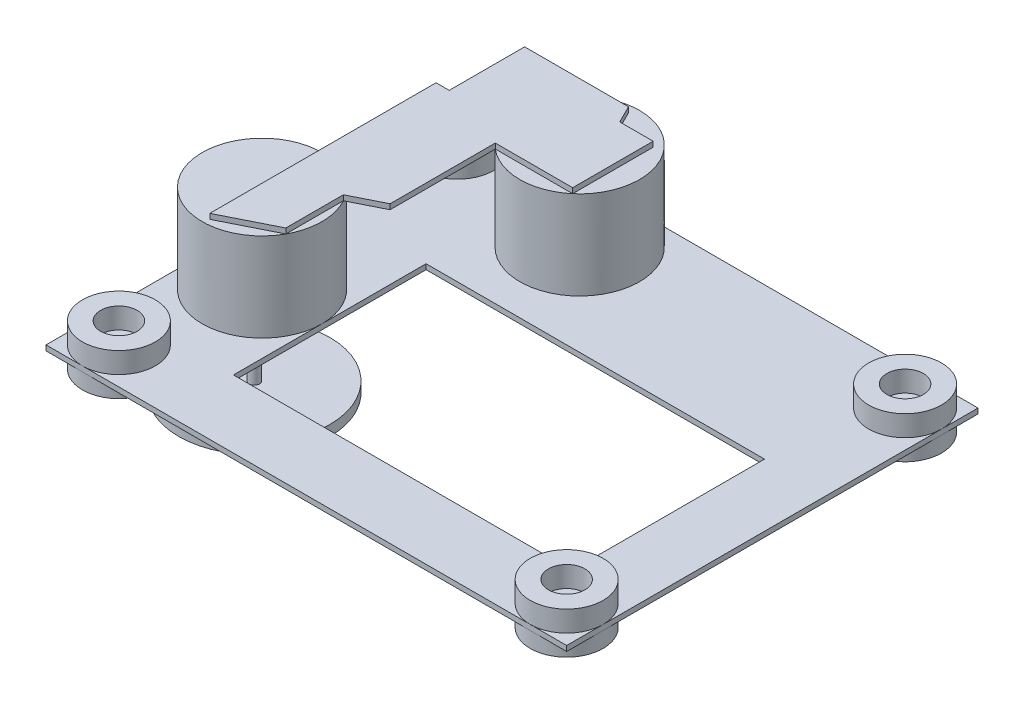
SolidWorks part; units mm, degrees
ref_plane "Plan de face" through (0, 0, 0) normal (0, 0, 1) x (1, 0, 0)
ref_plane "Plan de dessus" through (0, 0, 0) normal (0, 1, 0) x (1, 0, 0)
ref_plane "Plan de droite" through (0, 0, 0) normal (1, 0, 0) x (0, 0, -1)
sketch "Esquisse4" plane through (0, 0, 0) normal (0, 1, 0) x (1, 0, 0)
  line L1 (-50, -39.5) -> (50, -39.5)
  line L2 (-50, -39.5) -> (-50, 39.5)
  line L3 (-50, 39.5) -> (50, 39.5)
  line L4 (50, -39.5) -> (50, 39.5)
  line L5 (-50, -39.5) -> (50, 39.5) construction
  line L6 (-50, 39.5) -> (50, -39.5) construction
  point P0 (0, 0)
  dimension "D1" = 100
  dimension "D2" = 79
extrude "Boss.-Extru.3" add sketch "Esquisse4" against normal blind 1
sketch "Esquisse1" plane through (0, 0, 0) normal (0, 1, 0) x (1, 0, 0)
  line L0 (36, 39.5) -> (36, 25.5) construction
  line L1 (-50, -39.5) -> (50, -39.5)
  line L2 (-50, -39.5) -> (-50, 39.5)
  line L3 (-50, 39.5) -> (50, 39.5)
  line L4 (50, -39.5) -> (50, 39.5)
  line L5 (-50, -39.5) -> (50, 39.5) construction
  line L6 (-50, 39.5) -> (50, -39.5) construction
  line L7 (36, 25.5) -> (50, 25.5) construction
  line L8 (36, 25.5) -> (50, 39.5) construction
  line L9 (-36, 39.5) -> (-36, 25.5) construction
  line L10 (-36, 25.5) -> (-50, 25.5) construction
  line L11 (-36, 25.5) -> (-50, 39.5) construction
  line L12 (-50, -25.5) -> (-36, -25.5) construction
  line L13 (-36, -25.5) -> (-36, -39.5) construction
  line L14 (-36, -25.5) -> (-50, -39.5) construction
  line L15 (50, -25.5) -> (36, -25.5) construction
  line L16 (36, -25.5) -> (36, -39.5) construction
  line L17 (36, -25.5) -> (50, -39.5) construction
  circle A0 centre (43, 32.5) radius 7
  circle A1 centre (-43, 32.5) radius 7
  circle A2 centre (-43, -32.5) radius 7
  circle A3 centre (43, -32.5) radius 7
  circle A4 centre (-43, 32.5) radius 3.5
  circle A5 centre (43, 32.5) radius 3.5
  circle A6 centre (43, -32.5) radius 3.5
  circle A7 centre (-43, -32.5) radius 3.5
  point P0 (0, 0)
  dimension "D4" = 14
  dimension "D5" = 14
  dimension "D12" = 7
  dimension "D13" = 7
  dimension "D14" = 7
  dimension "D15" = 7
  dimension "D1" = 100
  dimension "D2" = 79
  dimension "D3" = 14
  dimension "D6" = 14
  dimension "D7" = 14
  dimension "D8" = 14
  dimension "D9" = 14
  dimension "D10" = 14
  dimension "D11" = 14
extrude "Boss.-Extru.4" add sketch "Esquisse1" against normal blind 4 and the other way blind 4 contours A0 | A1 | A2 | A3 region at (-47.8097, 0, 37.3097) region at (38.1903, 0, 27.6903) region at (-47.8097, 0, -37.3097) region at (38.1903, 0, -27.6903)
sketch "Esquisse6" plane through (0, 0, 0) normal (0, 1, 0) x (1, 0, 0)
  line L0 (-38.5, -9.5) -> (-50, -9.5) construction
  line L1 (-50, 32.5) -> (-50, -32.5) construction
  line L2 (-38.5, -9.5) -> (-38.5, -39.5) construction
  line L3 (-43, -39.5) -> (43, -39.5) construction
  line L4 (-15, 28) -> (-15, 39.5) construction
  line L5 (43, 39.5) -> (-43, 39.5) construction
  line L6 (-15, 28) -> (-50, 28) construction
  circle A0 centre (-38.5, -9.5) radius 11.5
  circle A1 centre (-15, 28) radius 11.5
  dimension "D1" = 23
  dimension "D2" = 23
  dimension "D3" = 11.5
  dimension "D4" = 30
  dimension "D5" = 11.5
  dimension "D6" = 35
extrude "Boss.-Extru.5" add sketch "Esquisse6" along normal blind 17
sketch "Esquisse7" plane through (0, 17, 0) normal (0, 1, 0) x (1, 0, 0)
  line L0 (-38.1438, -19.8875) -> (-28.4142, -15.0251)
  line L1 (-28.4142, -15.0251) -> (-28.4142, -3.9749)
  line L2 (-28.4142, -3.9749) -> (-22.4283, -0.9834)
  line L3 (-22.4283, -0.9834) -> (-22.4283, 19.221)
  line L4 (-22.4283, 19.221) -> (-7.5717, 19.221)
  line L5 (-7.5717, 19.221) -> (-7.5717, 34.6801)
  line L6 (-7.5717, 34.6801) -> (-13.9887, 34.6801)
  line L7 (-13.9887, 34.6801) -> (-15.6674, 38.0391)
  line L8 (-15.6674, 38.0391) -> (-35.6132, 38.0391)
  line L9 (-35.6132, 38.0391) -> (-35.6132, 23.5595)
  line L12 (-38.1438, 23.5595) -> (-38.1438, 0)
  line L13 (-38.1438, 0) -> (-38.1438, -19.8875)
  line L14 (-38.1438, 23.5595) -> (-35.6132, 23.5595)
  circle A0 centre (-38.5, -9.5) radius 11.5 construction
  circle A1 centre (-38.5, -9.5) radius 11.5 construction
  circle A2 centre (-15, 28) radius 11.5 construction
  circle A3 centre (-15, 28) radius 11.5 construction
extrude "Boss.-Extru.6" add sketch "Esquisse7" along normal blind 1
sketch "Esquisse8" plane through (0, 0, 0) normal (0, 1, 0) x (1, 0, 0)
  line L0 (-43, -39.5) -> (43, -39.5) construction
  line L1 (-27, -26.5) -> (38, -26.5)
  line L2 (-27, -26.5) -> (-27, 10.5)
  line L3 (-27, 10.5) -> (38, 10.5)
  line L4 (38, -26.5) -> (38, 10.5)
  line L5 (50, -32.5) -> (50, 32.5) construction
  dimension "D1" = 13
  dimension "D2" = 37
  dimension "D3" = 65
  dimension "D4" = 12
extrude "Enlèv. mat.-Extru.1" cut sketch "Esquisse8" against normal blind 1
sketch "Esquisse9" plane through (0, -1, 0) normal (0, -1, 0) x (1, 0, 0)
  line L1 (-50, -32.5) -> (-50, 32.5) construction
  line L4 (-43, 39.5) -> (43, 39.5) construction
  circle A0 centre (-40, 9.5) radius 1
  dimension "D1" = 2
  dimension "D2" = 30
  dimension "D3" = 10
extrude "Boss.-Extru.7" add sketch "Esquisse9" along normal blind 15
sketch "Esquisse10" plane through (0, -16, 0) normal (0, -1, 0) x (1, 0, 0)
  circle A0 centre (-40, 9.5) radius 14.5
  dimension "D1" = 29
extrude "Boss.-Extru.8" add sketch "Esquisse10" along normal blind 2
sketch "Esquisse11" plane through (0, -18, 0) normal (0, -1, 0) x (-1, 0, 0)
  line L0 (25.5, -9.5) -> (54.5, -9.5) construction
  circle A0 centre (40, -9.5) radius 14.5 construction
  circle A1 centre (40, -9.5) radius 7.5
  dimension "D1" = 15
extrude "Boss.-Extru.9" add sketch "Esquisse11" along normal blind 4
fillet "Congé1" radius 3 1 edges at (-40, -22, 2)
